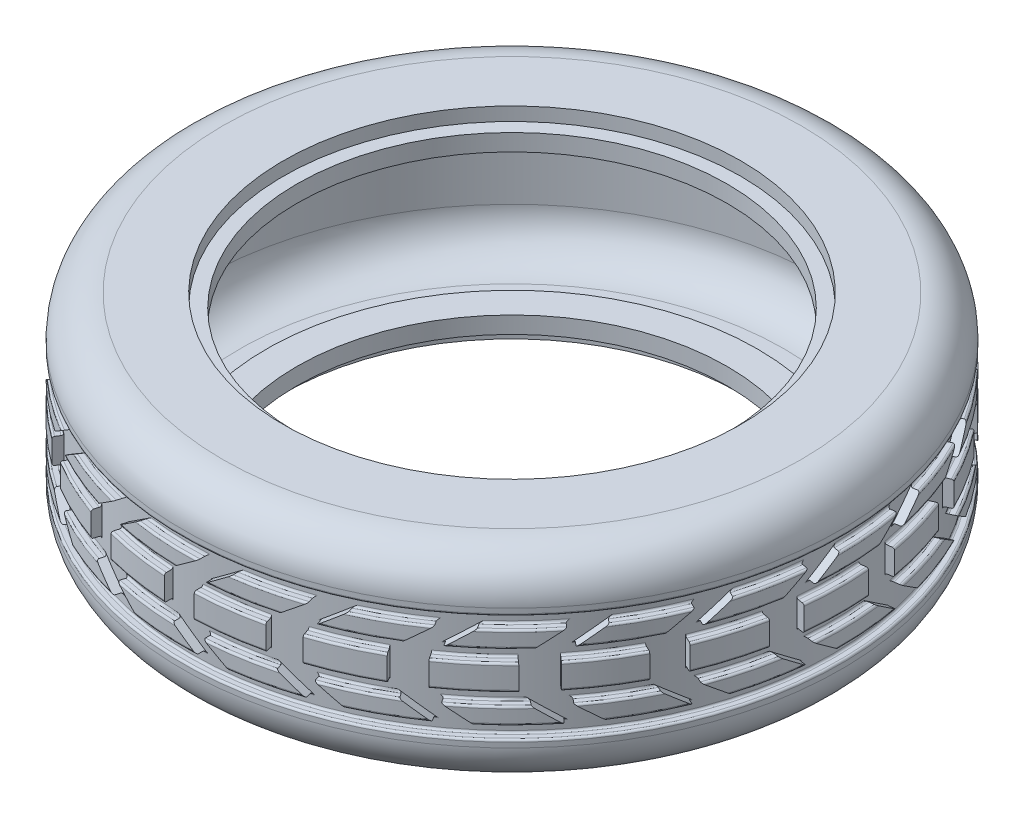
SolidWorks part; units mm, degrees
ref_plane "Front Plane" through (0, 0, 0) normal (0, 0, 1) x (1, 0, 0)
ref_plane "Top Plane" through (0, 0, 0) normal (0, 1, 0) x (1, 0, 0)
ref_plane "Right Plane" through (0, 0, 0) normal (1, 0, 0) x (0, 0, -1)
sketch "Sketch1" plane through (0, 0, 0) normal (0, 0, 1) x (1, 0, 0)
  line L0 (0, 0) -> (0, 322.0779) construction
  line L1 (-320, 9.5584) -> (-320, 34.5584)
  line L2 (-320, 269.5584) -> (-340, 269.5584)
  line L3 (-340, 269.5584) -> (-340, 289.5584)
  line L4 (-340, 289.5584) -> (-430, 289.5584)
  line L5 (-490, 229.5584) -> (-490, 222.2123)
  line L6 (-430, -10.4416) -> (-340, -10.4416)
  line L7 (-340, -10.4416) -> (-340, 9.5584)
  line L8 (-340, 9.5584) -> (-320, 9.5584)
  line L9 (-465, 204.5584) -> (-465, 74.5584)
  line L10 (-405, 14.5584) -> (-365, 14.5584)
  line L11 (-365, 14.5584) -> (-365, 34.5584)
  line L12 (-365, 34.5584) -> (-345, 34.5584)
  line L14 (-345, 244.5584) -> (-365, 244.5584)
  line L15 (-365, 244.5584) -> (-365, 264.5584)
  line L16 (-365, 264.5584) -> (-405, 264.5584)
  line L17 (-345, 244.5584) -> (-320, 244.5584)
  line L18 (-345, 34.5584) -> (-320, 34.5584)
  line L19 (-320, 244.5584) -> (-320, 269.5584)
  line L28 (-345, 34.5584) -> (-345, 244.5584) construction
  line L29 (-320, 9.5584) -> (-320, 269.5584) construction
  line L30 (-490, 289.5584) -> (-490, -10.4416) construction
  line L31 (-490, -10.4416) -> (-340, -10.4416) construction
  line L32 (-465, 264.5584) -> (-465, 14.5584) construction
  line L33 (-465, 14.5584) -> (-365, 14.5584) construction
  line L34 (-365, 264.5584) -> (-465, 264.5584) construction
  line L35 (-340, 289.5584) -> (-490, 289.5584) construction
  line L36 (-490, 198.2123) -> (-490, 179.291)
  line L37 (-477.0736, 105.8259) -> (-477.0736, 117.8259)
  line L38 (-487, 219.2123) -> (-480.0736, 219.2123)
  line L40 (-487, 201.2123) -> (-480.0736, 201.2123)
  line L41 (-477.0736, 216.2123) -> (-477.0736, 204.2123)
  line L42 (-487, 176.291) -> (-480.0736, 176.291)
  line L44 (-487, 158.291) -> (-480.0736, 158.291)
  line L45 (-477.0736, 173.291) -> (-477.0736, 161.291)
  line L46 (-487, 120.8259) -> (-480.0736, 120.8259)
  line L47 (-487, 102.8259) -> (-480.0736, 102.8259)
  line L48 (-477.0736, 62.9046) -> (-477.0736, 74.9046)
  line L49 (-487, 77.9046) -> (-480.0736, 77.9046)
  line L50 (-487, 59.9046) -> (-480.0736, 59.9046)
  line L51 (-490, 155.291) -> (-490, 123.8259)
  line L52 (-490, 99.8259) -> (-490, 80.9046)
  line L53 (-490, 56.9046) -> (-490, 49.5584)
  arc A0 (-490, 49.5584) -> (-430, -10.4416) centre (-430, 49.5584) ccw
  arc A1 (-465, 74.5584) -> (-405, 14.5584) centre (-405, 74.5584) ccw
  arc A2 (-465, 204.5584) -> (-405, 264.5584) centre (-405, 204.5584) cw
  arc A3 (-430, 289.5584) -> (-490, 229.5584) centre (-430, 229.5584) ccw
  arc A4 (-487, 59.9046) -> (-490, 56.9046) centre (-487, 56.9046) ccw
  arc A5 (-477.0736, 62.9046) -> (-480.0736, 59.9046) centre (-480.0736, 62.9046) cw
  arc A6 (-477.0736, 74.9046) -> (-480.0736, 77.9046) centre (-480.0736, 74.9046) ccw
  arc A7 (-487, 77.9046) -> (-490, 80.9046) centre (-487, 80.9046) cw
  arc A8 (-487, 102.8259) -> (-490, 99.8259) centre (-487, 99.8259) ccw
  arc A9 (-477.0736, 105.8259) -> (-480.0736, 102.8259) centre (-480.0736, 105.8259) cw
  arc A10 (-477.0736, 117.8259) -> (-480.0736, 120.8259) centre (-480.0736, 117.8259) ccw
  arc A11 (-487, 120.8259) -> (-490, 123.8259) centre (-487, 123.8259) cw
  arc A12 (-480.0736, 158.291) -> (-477.0736, 161.291) centre (-480.0736, 161.291) ccw
  arc A13 (-487, 158.291) -> (-490, 155.291) centre (-487, 155.291) ccw
  arc A14 (-480.0736, 176.291) -> (-477.0736, 173.291) centre (-480.0736, 173.291) cw
  arc A15 (-487, 176.291) -> (-490, 179.291) centre (-487, 179.291) cw
  arc A16 (-487, 201.2123) -> (-490, 198.2123) centre (-487, 198.2123) ccw
  arc A17 (-480.0736, 201.2123) -> (-477.0736, 204.2123) centre (-480.0736, 204.2123) ccw
  arc A18 (-480.0736, 219.2123) -> (-477.0736, 216.2123) centre (-480.0736, 216.2123) cw
  arc A19 (-487, 219.2123) -> (-490, 222.2123) centre (-487, 222.2123) cw
  point P39 (-490, 59.9046)
  point P58 (-490, 77.9046)
  point P61 (-490, 102.8259)
  point P68 (-490, 120.8259)
  point P73 (-490, 158.291)
  point P78 (-490, 176.291)
  point P81 (-490, 201.2123)
  dimension "D9" = 60
  dimension "D5" = 3
  dimension "D1" = 320
  dimension "D2" = 260
  dimension "D3" = 20
  dimension "D4" = 20
  dimension "D6" = 20
  dimension "D7" = 20
  dimension "D8" = 25
revolve "Revolve1" add sketch "Sketch1" angle 360 about L0
ref_plane "Plane1" through (0, 0, 510) normal (0, 0, 1) x (1, 0, 0)
sketch "Sketch3" plane through (0, 0, 510) normal (0, 0, 1) x (1, 0, 0)
  line L0 (0, 138.6753) -> (155.5112, 138.6753) construction
  line L1 (79.3649, 67.8702) -> (34.3649, 67.8702)
  line L2 (79.3649, 67.8702) -> (17.1547, 112.0722)
  line L3 (34.3649, 67.8702) -> (-27.8453, 112.0722)
  line L5 (34.3649, 209.4803) -> (-27.8453, 165.2783)
  line L7 (79.3649, 209.4803) -> (17.1547, 165.2783)
  line L8 (79.3649, 209.4803) -> (34.3649, 209.4803)
  line L9 (-27.8453, 165.2783) -> (-27.8453, 112.0722)
  line L10 (17.1547, 165.2783) -> (17.1547, 112.0722)
  dimension "D1" = 45
extrude "Cut-Extrude2" cut sketch "Sketch3" against normal up to surface (39.5742 mm away) contours L7 L10 L2 L1 L3 L9 L5 L8 up to face at (0, 161.291, -477.0736)
pattern_circular "CirPattern1" count 22 over 360 about axis through (0, 0, 0) along (0, -1, 0) of "Cut-Extrude2"
